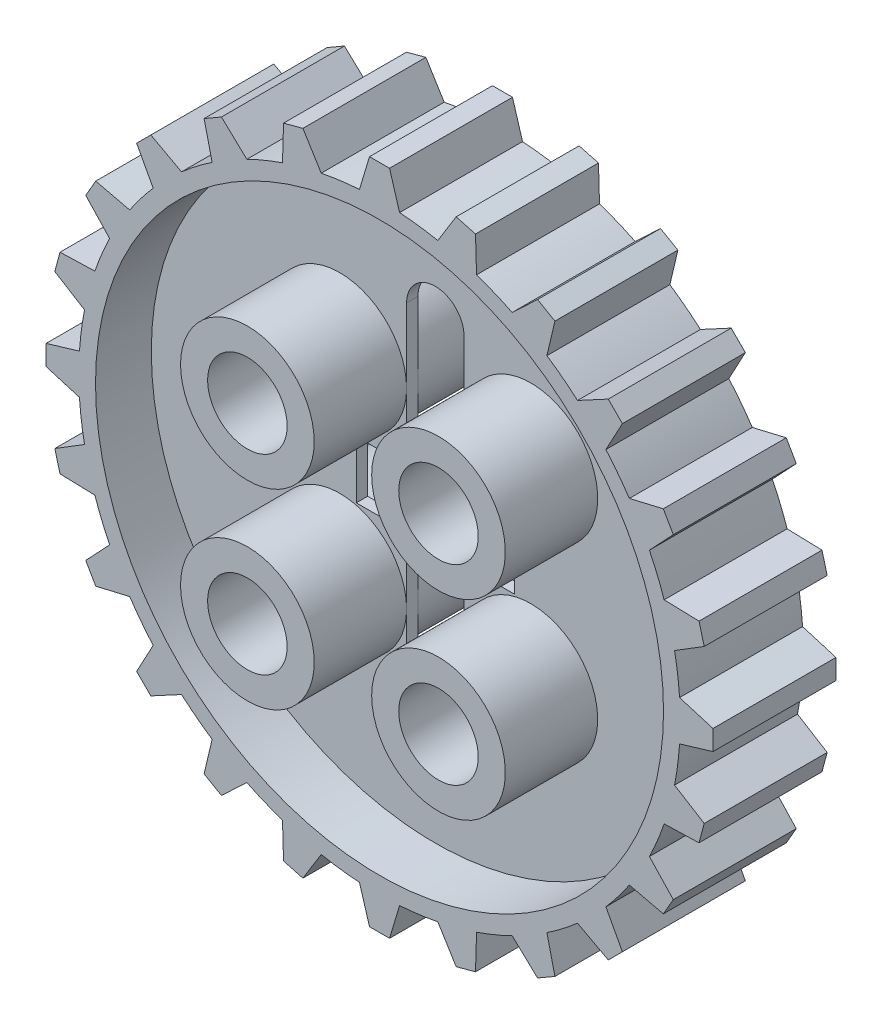
SolidWorks part; units mm, degrees
ref_plane "Front Plane" through (0, 0, 0) normal (0, 0, 1) x (1, 0, 0)
ref_plane "Top Plane" through (0, 0, 0) normal (0, 1, 0) x (1, 0, 0)
ref_plane "Right Plane" through (0, 0, 0) normal (1, 0, 0) x (0, 0, -1)
sketch "Sketch1" plane through (0, 0, 0) normal (0, 0, 1) x (1, 0, 0)
  line L0 (0, 0) -> (0, 20.1411) construction
  line L1 (0.6, 8.98) -> (0.3, 9.98)
  line L2 (0.3, 9.98) -> (-0.3, 9.98)
  line L3 (-0.6, 8.98) -> (-0.3, 9.98)
  line L4 (1.7446, 8.8293) -> (2.2932, 9.7176)
  line L5 (2.8728, 9.5623) -> (2.2932, 9.7176)
  line L6 (2.9037, 8.5187) -> (2.8728, 9.5623)
  line L7 (3.9704, 8.0769) -> (4.7302, 8.7929)
  line L8 (5.2498, 8.4929) -> (4.7302, 8.7929)
  line L9 (5.0096, 7.4769) -> (5.2498, 8.4929)
  line L10 (5.9255, 6.7741) -> (6.8448, 7.269)
  line L11 (7.269, 6.8448) -> (6.8448, 7.269)
  line L12 (6.7741, 5.9255) -> (7.269, 6.8448)
  line L13 (7.4769, 5.0096) -> (8.4929, 5.2498)
  line L14 (8.7929, 4.7302) -> (8.4929, 5.2498)
  line L15 (8.0769, 3.9704) -> (8.7929, 4.7302)
  line L16 (8.5187, 2.9037) -> (9.5623, 2.8728)
  line L17 (9.7176, 2.2932) -> (9.5623, 2.8728)
  line L18 (8.8293, 1.7446) -> (9.7176, 2.2932)
  line L19 (8.98, 0.6) -> (9.98, 0.3)
  line L20 (9.98, -0.3) -> (9.98, 0.3)
  line L21 (8.98, -0.6) -> (9.98, -0.3)
  line L22 (8.8293, -1.7446) -> (9.7176, -2.2932)
  line L23 (9.5623, -2.8728) -> (9.7176, -2.2932)
  line L24 (8.5187, -2.9037) -> (9.5623, -2.8728)
  line L25 (8.0769, -3.9704) -> (8.7929, -4.7302)
  line L26 (8.4929, -5.2498) -> (8.7929, -4.7302)
  line L27 (7.4769, -5.0096) -> (8.4929, -5.2498)
  line L28 (6.7741, -5.9255) -> (7.269, -6.8448)
  line L29 (6.8448, -7.269) -> (7.269, -6.8448)
  line L30 (5.9255, -6.7741) -> (6.8448, -7.269)
  line L31 (5.0096, -7.4769) -> (5.2498, -8.4929)
  line L32 (4.7302, -8.7929) -> (5.2498, -8.4929)
  line L33 (3.9704, -8.0769) -> (4.7302, -8.7929)
  line L34 (2.9037, -8.5187) -> (2.8728, -9.5623)
  line L35 (2.2932, -9.7176) -> (2.8728, -9.5623)
  line L36 (1.7446, -8.8293) -> (2.2932, -9.7176)
  line L37 (0.6, -8.98) -> (0.3, -9.98)
  line L38 (-0.3, -9.98) -> (0.3, -9.98)
  line L39 (-0.6, -8.98) -> (-0.3, -9.98)
  line L40 (-1.7446, -8.8293) -> (-2.2932, -9.7176)
  line L41 (-2.8728, -9.5623) -> (-2.2932, -9.7176)
  line L42 (-2.9037, -8.5187) -> (-2.8728, -9.5623)
  line L43 (-3.9704, -8.0769) -> (-4.7302, -8.7929)
  line L44 (-5.2498, -8.4929) -> (-4.7302, -8.7929)
  line L45 (-5.0096, -7.4769) -> (-5.2498, -8.4929)
  line L46 (-5.9255, -6.7741) -> (-6.8448, -7.269)
  line L47 (-7.269, -6.8448) -> (-6.8448, -7.269)
  line L48 (-6.7741, -5.9255) -> (-7.269, -6.8448)
  line L49 (-7.4769, -5.0096) -> (-8.4929, -5.2498)
  line L50 (-8.7929, -4.7302) -> (-8.4929, -5.2498)
  line L51 (-8.0769, -3.9704) -> (-8.7929, -4.7302)
  line L52 (-8.5187, -2.9037) -> (-9.5623, -2.8728)
  line L53 (-9.7176, -2.2932) -> (-9.5623, -2.8728)
  line L54 (-8.8293, -1.7446) -> (-9.7176, -2.2932)
  line L55 (-8.98, -0.6) -> (-9.98, -0.3)
  line L56 (-9.98, 0.3) -> (-9.98, -0.3)
  line L57 (-8.98, 0.6) -> (-9.98, 0.3)
  line L58 (-8.8293, 1.7446) -> (-9.7176, 2.2932)
  line L59 (-9.5623, 2.8728) -> (-9.7176, 2.2932)
  line L60 (-8.5187, 2.9037) -> (-9.5623, 2.8728)
  line L61 (-8.0769, 3.9704) -> (-8.7929, 4.7302)
  line L62 (-8.4929, 5.2498) -> (-8.7929, 4.7302)
  line L63 (-7.4769, 5.0096) -> (-8.4929, 5.2498)
  line L64 (-6.7741, 5.9255) -> (-7.269, 6.8448)
  line L65 (-6.8448, 7.269) -> (-7.269, 6.8448)
  line L66 (-5.9255, 6.7741) -> (-6.8448, 7.269)
  line L67 (-5.0096, 7.4769) -> (-5.2498, 8.4929)
  line L68 (-4.7302, 8.7929) -> (-5.2498, 8.4929)
  line L69 (-3.9704, 8.0769) -> (-4.7302, 8.7929)
  line L70 (-2.9037, 8.5187) -> (-2.8728, 9.5623)
  line L71 (-2.2932, 9.7176) -> (-2.8728, 9.5623)
  line L72 (-1.7446, 8.8293) -> (-2.2932, 9.7176)
  arc A0 (-5.0096, 7.4769) -> (-5.9255, 6.7741) centre (0, 0) ccw
  arc A1 (-2.9037, 8.5187) -> (-3.9704, 8.0769) centre (0, 0) ccw
  arc A2 (-0.6, 8.98) -> (-1.7446, 8.8293) centre (0, 0) ccw
  arc A3 (1.7446, 8.8293) -> (0.6, 8.98) centre (0, 0) ccw
  arc A4 (3.9704, 8.0769) -> (2.9037, 8.5187) centre (0, 0) ccw
  arc A5 (5.9255, 6.7741) -> (5.0096, 7.4769) centre (0, 0) ccw
  arc A6 (7.4769, 5.0096) -> (6.7741, 5.9255) centre (0, 0) ccw
  arc A7 (8.5187, 2.9037) -> (8.0769, 3.9704) centre (0, 0) ccw
  arc A8 (8.98, 0.6) -> (8.8293, 1.7446) centre (0, 0) ccw
  arc A9 (8.8293, -1.7446) -> (8.98, -0.6) centre (0, 0) ccw
  arc A10 (8.0769, -3.9704) -> (8.5187, -2.9037) centre (0, 0) ccw
  arc A11 (6.7741, -5.9255) -> (7.4769, -5.0096) centre (0, 0) ccw
  arc A12 (5.0096, -7.4769) -> (5.9255, -6.7741) centre (0, 0) ccw
  arc A13 (2.9037, -8.5187) -> (3.9704, -8.0769) centre (0, 0) ccw
  arc A14 (0.6, -8.98) -> (1.7446, -8.8293) centre (0, 0) ccw
  arc A15 (-1.7446, -8.8293) -> (-0.6, -8.98) centre (0, 0) ccw
  arc A16 (-3.9704, -8.0769) -> (-2.9037, -8.5187) centre (0, 0) ccw
  arc A17 (-5.9255, -6.7741) -> (-5.0096, -7.4769) centre (0, 0) ccw
  arc A18 (-7.4769, -5.0096) -> (-6.7741, -5.9255) centre (0, 0) ccw
  arc A19 (-8.5187, -2.9037) -> (-8.0769, -3.9704) centre (0, 0) ccw
  arc A20 (-8.98, -0.6) -> (-8.8293, -1.7446) centre (0, 0) ccw
  arc A21 (-8.8293, 1.7446) -> (-8.98, 0.6) centre (0, 0) ccw
  arc A22 (-8.0769, 3.9704) -> (-8.5187, 2.9037) centre (0, 0) ccw
  arc A23 (-6.7741, 5.9255) -> (-7.4769, 5.0096) centre (0, 0) ccw
  point P3 (0.6, 8.98)
  point P10 (0, 9.98)
  point P105 (0, 0)
  dimension "D1" = 18
  dimension "D2" = 0.6
  dimension "D3" = 0.3
  dimension "D4" = 1
  dimension "D5" = 24
extrude "Boss-Extrude1" add sketch "Sketch1" along normal blind 3.68
sketch "Sketch2" plane through (0, 0, 3.68) normal (0, 0, 1) x (1, 0, 0)
  circle A0 centre (0, 0) radius 8.5
  dimension "D1" = 17
extrude "Cut-Extrude1" cut sketch "Sketch2" against normal blind 1.67
sketch "Sketch3" plane through (0, 0, 0) normal (0, 0, -1) x (-1, 0, 0)
  circle A0 centre (0, 0) radius 8.5
  dimension "D1" = 17
extrude "Cut-Extrude2" cut sketch "Sketch3" against normal blind 1.67
sketch "Sketch17" plane through (0, 0, 1.67) normal (0, 0, -1) x (-1, 0, 0)
  line L0 (0, -5.075) -> (0, 5.075) construction
  line L1 (-7.0219, 0) -> (7.5701, 0) construction
  line L2 (-0.86, -5.075) -> (-0.86, 5.075)
  line L3 (0.86, -5.075) -> (0.86, 5.075)
  line L5 (-2.365, -0.86) -> (2.365, -0.86)
  line L6 (-2.365, -0.86) -> (-2.365, 0.86)
  line L7 (-2.365, 0.86) -> (2.365, 0.86)
  line L8 (2.365, -0.86) -> (2.365, 0.86)
  line L9 (-2.365, -0.86) -> (2.365, 0.86) construction
  line L10 (-2.365, 0.86) -> (2.365, -0.86) construction
  line L11 (-4.785, -2.62) -> (4.785, -2.62)
  line L12 (-4.785, -2.62) -> (-4.785, 2.62)
  line L13 (-4.785, 2.62) -> (4.785, 2.62)
  line L14 (4.785, -2.62) -> (4.785, 2.62)
  line L15 (-4.785, -2.62) -> (4.785, 2.62) construction
  line L16 (-4.785, 2.62) -> (4.785, -2.62) construction
  arc A2 (-0.86, -5.075) -> (0.86, -5.075) centre (0, -5.075) ccw
  arc A3 (0.86, 5.075) -> (-0.86, 5.075) centre (0, 5.075) ccw
  circle A4 centre (2.86, 2.86) radius 2
  circle A5 centre (2.86, -2.86) radius 2
  circle A6 centre (-2.86, -2.86) radius 2
  circle A7 centre (-2.86, 2.86) radius 2
  circle A8 centre (2.86, 2.86) radius 1.19
  circle A9 centre (-2.86, 2.86) radius 1.19
  circle A10 centre (-2.86, -2.86) radius 1.19
  circle A11 centre (2.86, -2.86) radius 1.19
  point P2 (0, 0)
  point P11 (0, 0)
  point P17 (0, 0)
  point P22 (2.86, 0.86)
  point P32 (0, 0)
  dimension "D1" = 10.15
  dimension "D3" = 1.72
  dimension "D4" = 4.73
  dimension "D5" = 9.57
  dimension "D7" = 4
  dimension "D2" = 1.72
  dimension "D6" = 5.24
  dimension "D9" = 0.81
  dimension "D8" = 4
extrude "Cut-Extrude3" cut sketch "Sketch17" against normal through all contours L3 A3 L2 L13 | L13 L2 L7 L3 | L7 L2 L5 L3 | L2 L11 L3 L5 | L2 A2 L3 L11 | L5 L8 L7 L3 | L7 L6 L5 L2 region at (0, -4.1911, 1.67) region at (0, -1.74, 1.67) region at (1.6125, 0, 1.67) region at (0, 0, 1.67) region at (0, 1.74, 1.67) region at (-1.6125, 0, 1.67) region at (0, 4.1911, 1.67)
extrude "Boss-Extrude6" add sketch "Sketch17<8>" along normal mid plane 6.21 contours A9 L13 A7 L12 | A9 L12 A7 L13 | A8 L14 A4 L13 | A8 L13 A4 L14 | A11 L11 A5 L14 | A11 L14 A5 L11 | A10 L11 A6 L12 | A10 L12 A6 L11 region at (3.1274, -4.7942, 1.67) region at (1.2845, -2.5771, 1.67) region at (-0.9109, -2.7426, 1.67) region at (3.1274, 4.7942, 1.67) region at (4.7421, 2.4687, 1.67) region at (-2.709, -0.9087, 1.67) region at (-2.709, 0.9087, 1.67) region at (-4.7897, 2.4687, 1.67)
sketch "Sketch17<8>" plane through (0, 0, 1.67) normal (0, 0, -1) x (-1, 0, 0) same geometry as "Sketch17"
